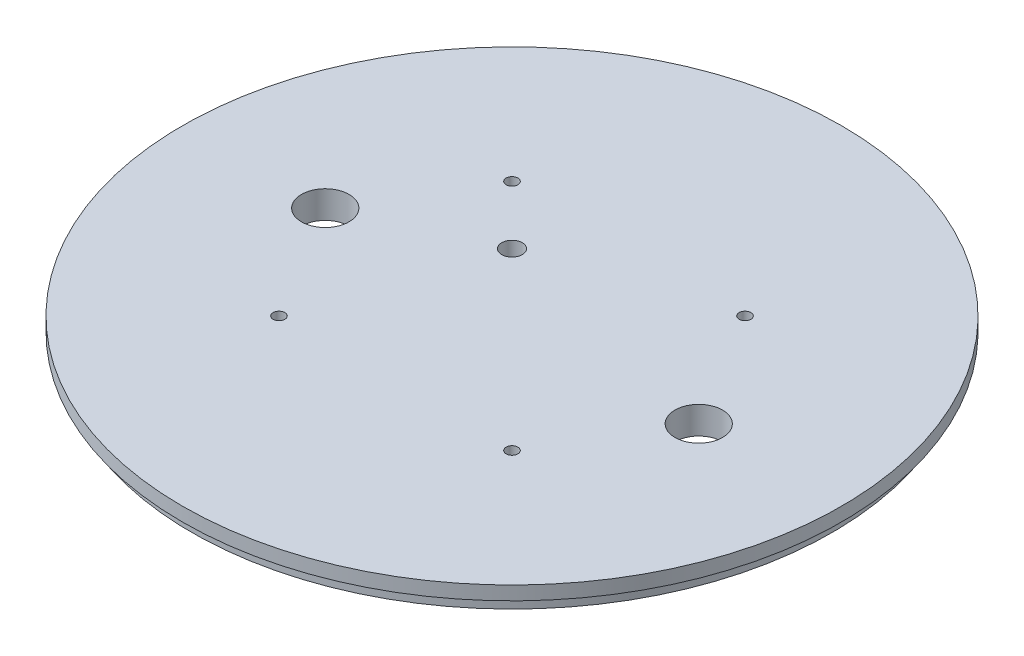
SolidWorks part; units mm, degrees
material "6061-T6 (SS)"
ref_plane "Front Plane" through (0, 0, 0) normal (0, 0, 1) x (1, 0, 0)
ref_plane "Top Plane" through (0, 0, 0) normal (0, 1, 0) x (1, 0, 0)
ref_plane "Right Plane" through (0, 0, 0) normal (1, 0, 0) x (0, 0, -1)
sketch "Sketch1" plane through (0, 0, 0) normal (0, 1, 0) x (1, 0, 0)
  line L0 (0, -76.2) -> (0, 76.2) construction
  line L1 (-76.2, 0) -> (76.2, 0) construction
  line L2 (-26.9408, 26.9408) -> (0, 0) construction
  line L3 (0, 56.7387) -> (0, 29.6936) construction
  line L4 (3.6407, 56.7387) -> (3.6407, 29.6936) construction
  line L5 (-3.6407, 56.7387) -> (-3.6407, 29.6936) construction
  line L6 (0, -56.7387) -> (0, -29.6936) construction
  line L7 (3.6407, -56.7387) -> (3.6407, -29.6936) construction
  line L8 (-3.6407, -56.7387) -> (-3.6407, -29.6936) construction
  line L9 (-53.8815, -53.8815) -> (54.3236, 54.3236) construction
  circle A0 centre (0, 0) radius 76.2
  circle A1 centre (0, 0) radius 3.175 construction
  circle A2 centre (43.18, 0) radius 5.5
  circle A3 centre (-43.18, 0) radius 5.5
  circle A4 centre (-26.9408, 26.9408) radius 1.3589
  arc A6 (3.6407, 56.7387) -> (-3.6407, 56.7387) centre (0, 56.7387) ccw construction
  arc A7 (-3.6407, 29.6936) -> (3.6407, 29.6936) centre (0, 29.6936) ccw construction
  arc A8 (3.6407, -56.7387) -> (-3.6407, -56.7387) centre (0, -56.7387) cw construction
  arc A9 (-3.6407, -29.6936) -> (3.6407, -29.6936) centre (0, -29.6936) cw construction
  circle A10 centre (26.9408, -26.9408) radius 1.3589
  circle A11 centre (-13.4704, 13.4704) radius 2.3813
  circle A12 centre (-26.9408, -26.9408) radius 1.3589
  circle A13 centre (26.9408, 26.9408) radius 1.3589
  circle A14 centre (-26.9408, 26.9408) radius 1.3589
  circle A15 centre (26.9408, -26.9408) radius 1.3589
  circle A16 centre (26.9408, 26.9408) radius 1.3589
  circle A17 centre (-26.9408, -26.9408) radius 1.3589
  point P16 (0, 43.2162)
  point P19 (0, 0)
  point P26 (0, -43.2162)
  point P50 (0, 0)
  dimension "D1" = 152.4
  dimension "D2" = 6.35
  dimension "D3" = 11
  dimension "D5" = 2.7178
  dimension "D8" = 4.7625
  dimension "D6" = 38.1
  dimension "D7" = 45
  dimension "D4" = 45
  dimension "D9" = 43.18
  dimension "D10" = 4
extrude "Boss-Extrude1" add sketch "Sketch1" along normal blind 6.35 contours A0 A13 A10 A4 A2 A3 A11 A12 region at (0.0133, 0, 0.0133)
sketch "Sketch2" plane through (0, 0, 0) normal (0, -1, 0) x (1, 0, 0)
  circle A0 centre (0, 0) radius 76.2
  circle A1 centre (0, 0) radius 74.041
  dimension "D1" = 152.4
  dimension "D2" = 148.082
extrude "Cut-Extrude1" cut sketch "Sketch2" against normal blind 3.175
sketch "Sketch3" plane through (0, 6.35, 0) normal (0, 1, 0) x (1, 0, 0)
  line L0 (0, 76.2) -> (0, -76.2) construction
  line L1 (-76.2, 0) -> (76.2, 0) construction
  line L2 (0, 34.798) -> (0, 13.97) construction
  line L3 (3.2385, 34.798) -> (3.2385, 13.97)
  line L4 (-3.2385, 34.798) -> (-3.2385, 13.97)
  line L5 (0, -34.798) -> (0, -13.97) construction
  line L6 (3.2385, -34.798) -> (3.2385, -13.97)
  line L7 (-3.2385, -34.798) -> (-3.2385, -13.97)
  circle A0 centre (0, 0) radius 76.2 construction
  arc A1 (3.2385, 34.798) -> (-3.2385, 34.798) centre (0, 34.798) ccw
  arc A2 (-3.2385, 13.97) -> (3.2385, 13.97) centre (0, 13.97) ccw
  arc A3 (3.2385, -34.798) -> (-3.2385, -34.798) centre (0, -34.798) cw
  arc A4 (-3.2385, -13.97) -> (3.2385, -13.97) centre (0, -13.97) cw
  point P7 (0, 13.97)
  point P8 (0, 34.798)
  point P12 (0, 24.384)
  point P20 (0, -24.384)
  point P25 (0, -34.798)
  point P26 (0, -13.97)
  dimension "D1" = 13.97
  dimension "D2" = 20.828
  dimension "D3" = 6.477
extrude "Cut-Extrude2" cut sketch "Sketch3" against normal blind 3.556 from offset 3.175 offset against normal yes
equation "\"leadDist\"=1.5"
equation "\"Lead_Screw_Dist\"= 3.4in"
equation "\"Lead_Screw_Diam\"= 11mm"
equation "\"D3@Sketch1\"=\"Lead_Screw_Diam\""
equation "\"D9@Sketch1\"=\"Lead_Screw_Dist\"/2"
